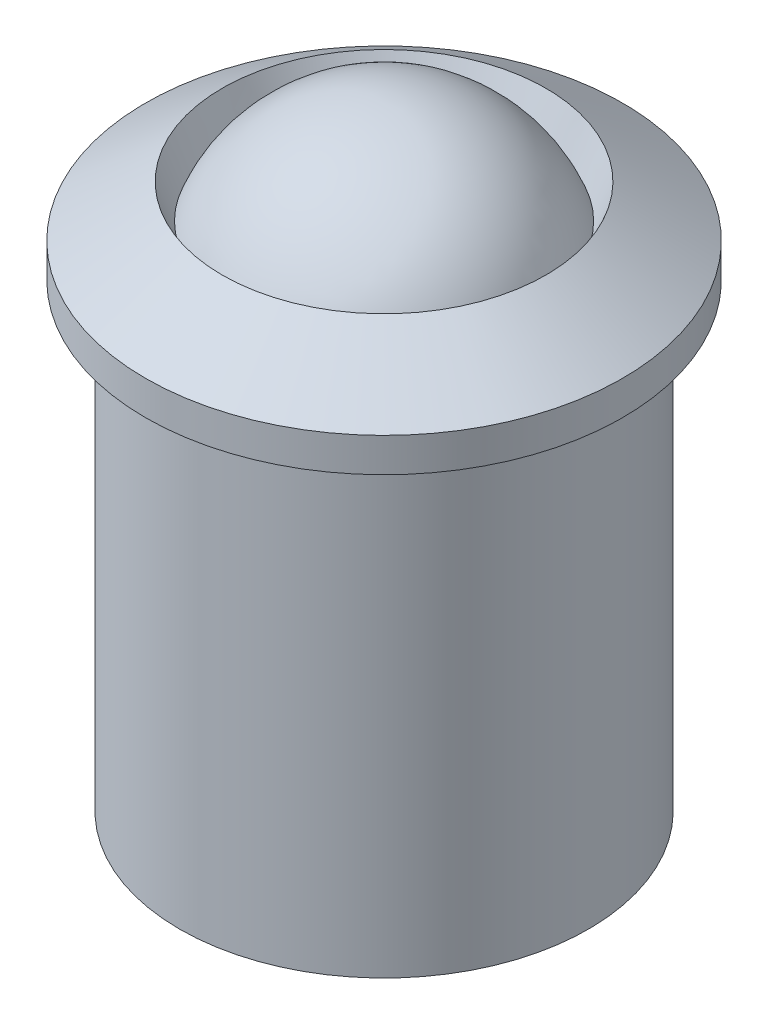
SolidWorks part; units mm, degrees
ref_plane "Front Plane" through (0, 0, 0) normal (0, 0, 1) x (1, 0, 0)
ref_plane "Top Plane" through (0, 0, 0) normal (0, 1, 0) x (1, 0, 0)
ref_plane "Right Plane" through (0, 0, 0) normal (1, 0, 0) x (0, 0, -1)
sketch "Sketch1" plane through (0, 0, 0) normal (1, 0, 0) x (0, 0, -1)
  line L0 (0, 0) -> (0, 18) construction
  line L1 (0, 0) -> (-6, 0)
  line L2 (-6, 0) -> (-6, 13.5)
  line L3 (-6, 13.5) -> (-7, 13.5)
  line L4 (-7, 13.5) -> (-7, 14.5)
  line L5 (0, 16) -> (-4.75, 16) construction
  line L6 (-4.75, 16) -> (-7, 14.5)
  line L7 (0, 15) -> (-4.35, 15)
  line L8 (-4.75, 16) -> (-4.35, 15)
  line L9 (0, 15) -> (0, 0)
  dimension "D1" = 18
  dimension "D2" = 12
  dimension "D3" = 13.5
  dimension "D4" = 14
  dimension "D5" = 1
  dimension "D6" = 9.5
  dimension "D7" = 1.5
  dimension "D8" = 1
  dimension "D9" = 8.7
revolve "Revolve1" add sketch "Sketch1" angle 360 about L9
sketch "Sketch5" plane through (0, 15, 0) normal (0, 1, 0) x (1, 0, 0)
  circle A1 centre (0, 0) radius 4.35
  circle A2 centre (0, 0) radius 4.35
  dimension "D1" = 0
dome "Dome2" faces to dome 1 distance 3 reverse direction no elliptical dome no face at (0, 15, 4.35) parameters "D1"=3
sketch "Sketch6" plane through (0, 0, 0) normal (0, -1, 0) x (1, 0, 0)
  circle A0 centre (0, 0) radius 5
  circle A1 centre (0, 0) radius 6
  circle A2 centre (0, 0) radius 6
  dimension "D1" = 0
  dimension "D2" = 1
extrude "Cut-Extrude1" cut sketch "Sketch6" against normal blind 7.5 contours A0 region at (0, 0, 0)
